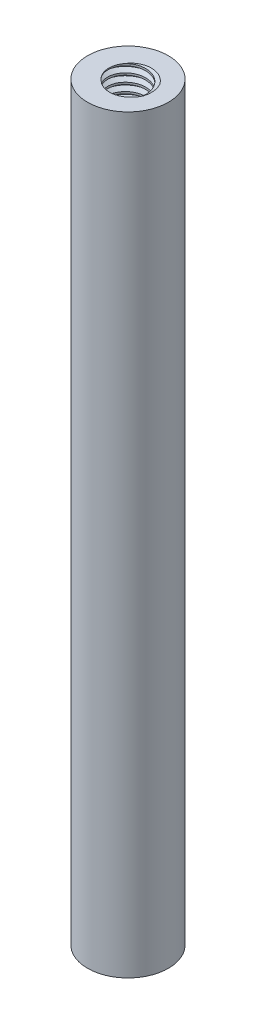
SolidWorks part; units mm, degrees
ref_plane "Front Plane" through (0, 0, 0) normal (0, 0, 1) x (1, 0, 0)
ref_plane "Top Plane" through (0, 0, 0) normal (0, 1, 0) x (1, 0, 0)
ref_plane "Right Plane" through (0, 0, 0) normal (1, 0, 0) x (0, 0, -1)
sketch "Sketch1" plane through (0, 0, 0) normal (0, 1, 0) x (1, 0, 0)
  circle A0 centre (0, 0) radius 3.5
  dimension "D1" = 7
extrude "Boss-Extrude1" add sketch "Sketch1" along normal mid plane 65
sketch "Sketch2" plane through (0, 32.5, 0) normal (0, 1, 0) x (1, 0, 0)
  circle A0 centre (0, 0) radius 1.65
  dimension "D1" = 3.3
extrude "Cut-Extrude1" cut sketch "Sketch2" against normal blind 6.5
thread "Thread1" pitch 0.7 method cut profile "Thread Profile1" start angle 0, offset 2, length 8, pitch 0.7, diameter 3.3
ref_plane "Plane1" through (-1.65, 34.5, 0) normal (0, 0, 1) x (-1, 0, 0)
sketch "Thread Profile1" plane through (-1.65, 34.5, 0) normal (0, 0, 1) x (-1, 0, 0)
  line L0 (0, 0) -> (0, 0.7) construction
  line L1 (0, 0) -> (0.3789, 0.2187)
  line L2 (0.3789, 0.2187) -> (0.3789, 0.3062)
  line L3 (0.3789, 0.3062) -> (0, 0.525)
  line L4 (0.3789, 0.2625) -> (0, 0.2625) construction
  line L11 (0, 0) -> (0, 0.525)
  point P2 (0, 0)
  dimension "Pitch" = 0.7
  dimension "Profile_Angle" = 60
  dimension "Profile_Land" = 0.0875
  dimension "Profile_Height" = 0.3789
mirror "Mirror3" about plane through (0, 0, 0) normal (0, 1, 0) of "Cut-Extrude1"
thread "Thread2" pitch 0.7 method cut profile "Thread Profile2" start angle 0, offset 2, length 8, pitch 0.7, diameter 3.3
ref_plane "Plane2" through (1.65, -34.5, 0) normal (0, 0, 1) x (1, 0, 0)
sketch "Thread Profile2" plane through (1.65, -34.5, 0) normal (0, 0, 1) x (1, 0, 0)
  line L0 (0, 0) -> (0, 0.7) construction
  line L1 (0, 0) -> (0.3789, 0.2187)
  line L2 (0.3789, 0.2187) -> (0.3789, 0.3062)
  line L3 (0.3789, 0.3062) -> (0, 0.525)
  line L4 (0.3789, 0.2625) -> (0, 0.2625) construction
  line L11 (0, 0) -> (0, 0.525)
  point P2 (0, 0)
  dimension "Pitch" = 0.7
  dimension "Profile_Angle" = 60
  dimension "Profile_Land" = 0.0875
  dimension "Profile_Height" = 0.3789
